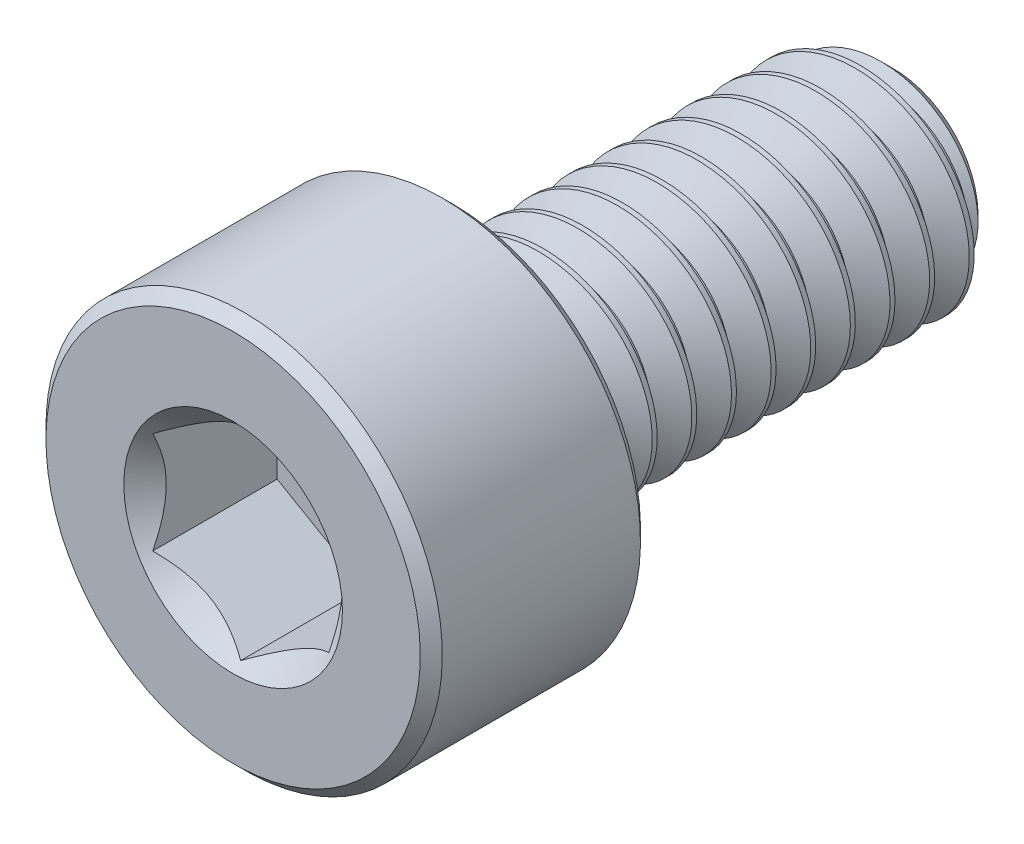
SolidWorks part; units mm, degrees
ref_plane "Front Plane" through (0, 0, 0) normal (0, 0, 1) x (1, 0, 0)
ref_plane "Top Plane" through (0, 0, 0) normal (0, 1, 0) x (1, 0, 0)
ref_plane "Right Plane" through (0, 0, 0) normal (1, 0, 0) x (0, 0, -1)
sketch "Sketch1" plane through (0, 0, 0) normal (1, 0, 0) x (0, 0, -1)
  line L0 (-3.75, 0) -> (3.75, 0) construction
  line L1 (3.75, 0) -> (3.75, 0.9577) construction
  line L2 (3.75, 0.9577) -> (3.4577, 1.25) construction
  line L3 (3.4577, 1.25) -> (3.4125, 1.25) construction
  line L4 (3.4125, 1.25) -> (-1.25, 1.25) construction
  line L5 (-1.25, 1.25) -> (-1.25, 2.25) construction
  line L6 (-1.25, 2.25) -> (-3.75, 2.25) construction
  line L7 (-3.75, 2.25) -> (-3.75, 0) construction
  line L8 (3.75, 0.9577) -> (3.75, 1.25) construction
  line L9 (3.7219, 1.2987) -> (3.9469, 0.909) construction
  line L10 (3.9469, 0.909) -> (4.1719, 1.2987) construction
  line L11 (4.1719, 1.2987) -> (3.7219, 1.2987) construction
  line L12 (3.9469, 1.2987) -> (3.9469, 1.25) construction
  line L13 (3.9469, 0.909) -> (3.9469, 0.9577) construction
  line L14 (3.9188, 0.9577) -> (3.975, 0.9577) construction
  line L15 (3.75, 1.25) -> (4.1438, 1.25) construction
  line L16 (3.7359, 1.2744) -> (4.1578, 1.2744) construction
  line L17 (3.75, 0) -> (3.75, -1.25) construction
  line L18 (-1.375, 2.25) -> (-1.25, 2.125) construction
  line L19 (-3.625, 2.25) -> (-3.75, 2.125) construction
  line L20 (-1.25, 1.25) -> (-1.25, 0) construction
  line L21 (-1.25, 0.625) -> (0.4167, 0.625) construction
  line L22 (0.4167, 0.625) -> (2.0833, 0.625) construction
  line L23 (2.0833, 0.625) -> (3.75, 0.625) construction
  line L24 (0.4167, 0.625) -> (0.4167, 1.25) construction
  line L25 (0.4167, 1.25) -> (0.4167, 2.25) construction
  line L26 (2.0833, 0.625) -> (2.0833, 2.25) construction
  point P0 (-3.75, 1)
  point P3 (2.625, 1.25)
  point P4 (0, 0)
  point P18 (2.0833, 1.25)
  point P22 (3.9469, 0.9577)
  point P24 (3.4125, 1.25)
  point P25 (3.9469, 1.25)
  point P28 (3.9469, 1.2744)
  point P29 (2.625, -1.25)
  point P30 (0.4167, 1.25)
  point P31 (-2.5, 2.25)
  point P37 (-1.6875, 2.25)
  point P38 (-3.5625, 2.25)
  point P45 (0.4167, 0.625)
  point P46 (2.0833, 0.625)
  dimension "D2" = 0.0563
  dimension "D7" = 0.125
  dimension "D8" = 0.125
  dimension "D9" = 0.125
  dimension "D10" = 0.0625
  dimension "D11" = 0.3125
  dimension "Drive Size" = 2
  dimension "Head Diameter" = 4.5
  dimension "Head Height" = 2.5
  dimension "Thread Pitch" = 0.45
  dimension "Thread Size" = 2.5
  dimension "Length" = 5
  dimension "D12" = 0.3375
  dimension "D4" = 1.125
  dimension "D3" = 45
sketch "Sketch2" plane through (0, 0, 0) normal (1, 0, 0) x (0, 0, -1)
  line L0 (-3.75, 0) -> (-3.75, 2.125)
  line L1 (-3.625, 2.25) -> (-1.375, 2.25)
  line L2 (-1.25, 2.125) -> (-1.25, 1.375)
  line L4 (3.4577, 1.25) -> (3.75, 0.9577)
  line L5 (3.75, 0.9577) -> (3.75, 0)
  line L6 (-1.25, 2.25) -> (-3.75, 2.25) construction
  line L7 (3.75, 0) -> (-3.75, 0)
  line L8 (-3.625, 2.25) -> (-3.75, 2.125) construction
  line L10 (-3.625, 2.25) -> (-3.75, 2.125)
  line L14 (-1.375, 2.25) -> (-1.25, 2.125) construction
  line L16 (-1.375, 2.25) -> (-1.25, 2.125)
  line L17 (-1.25, 1.25) -> (-1.25, 2.25) construction
  line L19 (-1.125, 1.25) -> (3.4577, 1.25)
  line L20 (3.4125, 1.25) -> (-1.25, 1.25) construction
  arc A1 (-1.25, 1.375) -> (-1.125, 1.25) centre (-1.125, 1.375) ccw
  dimension "D3" = 0.125
revolve "Revolve1" add sketch "Sketch2" angle 360 about L7
sketch "Sketch3" plane through (0, 0, 3.75) normal (0, 0, 1) x (1, 0, 0)
  line L1 (1, -0.5774) -> (1, 0.5774)
  line L2 (1, 0.5774) -> (0, 1.1547)
  line L3 (0, 1.1547) -> (-1, 0.5774)
  line L4 (-1, 0.5774) -> (-1, -0.5774)
  line L5 (-1, -0.5774) -> (0, -1.1547)
  line L6 (0, -1.1547) -> (1, -0.5774)
  circle A0 centre (0, 0) radius 1 construction
  circle A1 centre (0, 0) radius 2.25 construction
  circle A2 centre (0, 0) radius 2.25 construction
  circle A3 centre (0, 0) radius 1.1547 construction
  point P13 (0, 0)
  dimension "D1" = 2.3094
extrude "Cut-Extrude1" cut sketch "Sketch3" against normal offset from surface (1.5 mm away) 1 up to face at (0, 2.125, 1.25)
sketch "Sketch4" plane through (0, 0, 3.75) normal (0, 0, 1) x (1, 0, 0)
  circle A0 centre (0, 0) radius 1.2413
  dimension "D1" = 2.4826
extrude "Cut-Extrude2" cut sketch "Sketch4" against normal up to vertex (1.25 mm away) draft 45 up to point (0, 2.25, 2.5)
sketch "Sketch11" plane through (0, 0, 0) normal (1, 0, 0) x (0, 0, -1)
  line L0 (-3.75, 0) -> (3.75, 0) construction
  line L1 (-3.75, 0) -> (3.75, 0) construction
  line L2 (-0.3125, 0) -> (-0.3125, 1.25) construction
  line L3 (3.4125, 1.25) -> (-1.25, 1.25) construction
  line L4 (2.8125, 0) -> (2.8125, 1.25) construction
  line L6 (3.75, 0.9577) -> (3.75, 1.25) construction
  point P2 (-0.3125, 0)
  point P3 (2.8125, 0)
  dimension "D1" = 0.9375
  dimension "D2" = 0.9375
sketch "Sketch6" plane through (0, 0, -3.75) normal (0, 0, -1) x (-1, 0, 0)
  circle A0 centre (0, 0) radius 1.25
curve "Helix/Spiral1" pitch 0.45 height 5.45 turns 12.1111
sketch "Sketch10" plane through (0, 0, 0) normal (1, 0, 0) x (0, 0, -1)
  line L0 (-1.125, -2.25) -> (-1.125, 2.25)
  line L5 (-3.75, 0) -> (3.75, 0) construction
  line L6 (-1.125, 1.25) -> (-1.125, -1.25) construction
  point P3 (-1.125, 0)
split "Split1" trim tools "Sketch10" bodies to split 106 resulting bodies 114 115
sketch "Sketch7" plane through (0, 0, 0) normal (1, 0, 0) x (0, 0, -1)
  line L0 (3.7359, 1.2744) -> (4.1578, 1.2744)
  line L1 (4.1578, 1.2744) -> (3.975, 0.9577)
  line L2 (3.975, 0.9577) -> (3.9188, 0.9577)
  line L3 (3.9188, 0.9577) -> (3.7359, 1.2744)
sweep "Cut-Sweep1" cut profiles "Sketch7" path "Helix/Spiral1" align with end faces yes
sketch "Sketch8" plane through (0, 0, 0) normal (1, 0, 0) x (0, 0, -1)
  line L0 (-1.25, 0) -> (-1.25, 1.25)
  line L1 (-1.125, -1.25) -> (-1.125, 1.25) construction
  line L2 (-1.25, 1.25) -> (-1.125, 1.25)
  line L4 (-1.125, 1.25) -> (-0.4033, 0)
  line L5 (-0.4033, 0) -> (-1.25, 0)
  line L6 (3.4125, 1.25) -> (-1.25, 1.25) construction
  line L7 (-3.75, 0) -> (3.75, 0) construction
  dimension "D1" = 60
revolve "Revolve2" add sketch "Sketch8" angle 360 about L5
equation "\"D2@Sketch1\" = \"Thread Pitch@Sketch1\" / 8"
equation "\"D4@Helix/Spiral1\" = \"Thread Pitch@Sketch1\""
equation "\"D7@Sketch1\" = \"Head Height@Sketch1\" * .05"
equation "\"D8@Sketch1\"=\"D7@Sketch1\""
equation "\"D9@Sketch1\"=\"D7@Sketch1\""
equation "\"D10@Sketch1\"=\"D7@Sketch1\"/2"
equation "\"D11@Sketch1\"=\"D10@Sketch1\"*5"
equation "\"D4@Sketch1\"=\"Thread Pitch@Sketch1\"*2.5"
equation "\"D12@Sketch1\"=\"Thread Pitch@Sketch1\"*.75"
equation "\"D3@Helix/Spiral1\"=\"Length@Sketch1\"+\"Thread Pitch@Sketch1\""
equation "\"D3@Sketch2\"=\"Thread Size@Sketch1\"*0.05"
equation "\"D1@Sketch11\"=\"Length@Sketch1\"*0.1875"
equation "\"D2@Sketch11\"=\"D1@Sketch11\""
equation "\"D1@Sketch4\"=\"D1@Sketch3\"*1.075"
